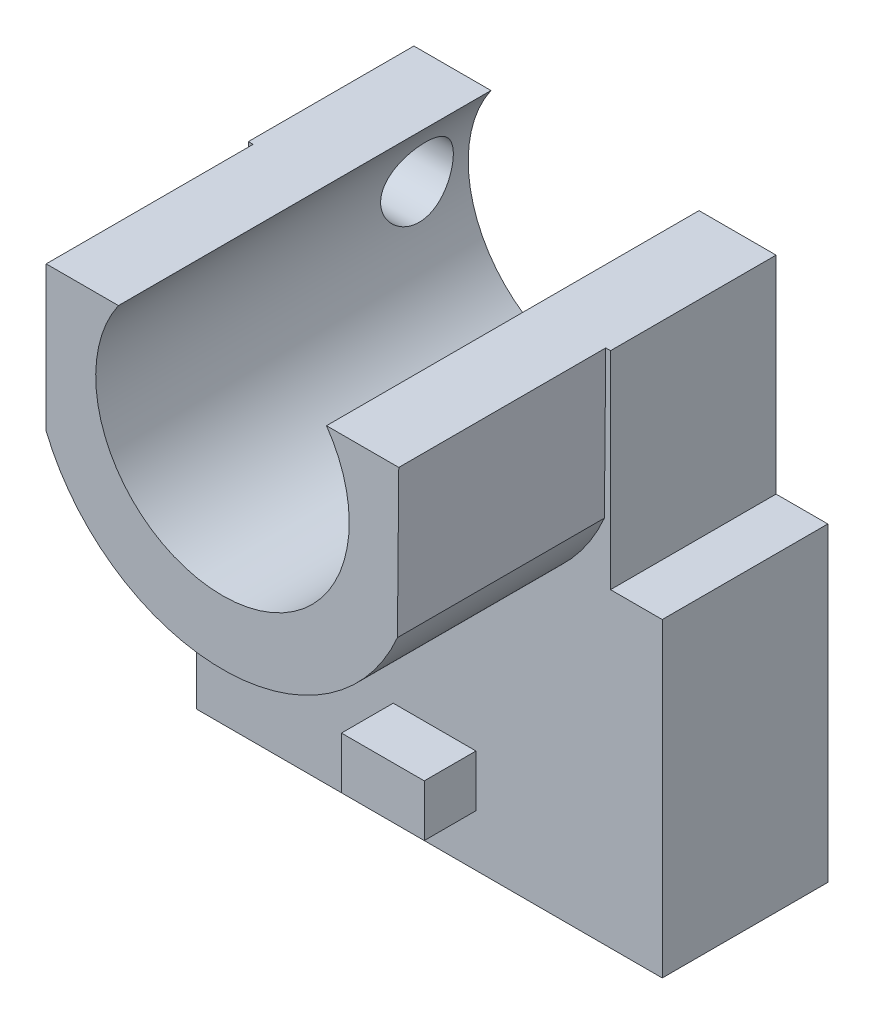
SolidWorks part; units mm, degrees
ref_plane "Front Plane" through (0, 0, 0) normal (0, 0, 1) x (1, 0, 0)
ref_plane "Top Plane" through (0, 0, 0) normal (0, 1, 0) x (1, 0, 0)
ref_plane "Right Plane" through (0, 0, 0) normal (1, 0, 0) x (0, 0, -1)
sketch "Sketch1" plane through (0, 0, 0) normal (0, 0, 1) x (1, 0, 0)
  line L0 (17.5, 15) -> (22.5, 15)
  line L1 (-22.5, -15) -> (22.5, -15)
  line L2 (-22.5, -15) -> (-22.5, 15)
  line L3 (-22.5, 15) -> (-17.5, 15)
  line L4 (22.5, -15) -> (22.5, 15)
  line L5 (-22.5, -15) -> (22.5, 15) construction
  line L6 (-22.5, 15) -> (22.5, -15) construction
  line L8 (-17.5, 15) -> (-17.5, 35)
  line L9 (-17.5, 35) -> (17.5, 35)
  line L10 (17.5, 15) -> (17.5, 35)
  point P0 (0, 0)
  dimension "D1" = 5
  dimension "D2" = 5
  dimension "D3" = 45
  dimension "D4" = 20
  dimension "D5" = 30
extrude "Boss-Extrude1" add sketch "Sketch1" along normal blind 16
sketch "Sketch2" plane through (0, 0, 16) normal (0, 0, 1) x (1, 0, 0)
  line L1 (4.5, -5) -> (-3.5, -5)
  line L2 (4.5, -5) -> (4.5, -10)
  line L3 (4.5, -10) -> (-3.5, -10)
  line L4 (-3.5, -5) -> (-3.5, -10)
  line L5 (4.5, -5) -> (-3.5, -10) construction
  line L6 (4.5, -10) -> (-3.5, -5) construction
  line L7 (-22.5, 15) -> (-22.5, -15) construction
  line L8 (-17.5, 15) -> (-22.5, 15) construction
  point P0 (0.5, -7.5)
  point P5 (0, 0)
  point P7 (0, 0)
  point P9 (-22.5, 0)
  point P12 (-20, 15)
  dimension "D1" = 8
  dimension "D2" = 5
  dimension "D3" = 19
  dimension "D4" = 20
extrude "Boss-Extrude2" add sketch "Sketch2" along normal blind 5 contours L3 L4 L1 L2
sketch "Sketch3" plane through (0, 0, 16) normal (0, 0, 1) x (1, 0, 0)
  line L0 (17.5, 35) -> (-17.5, 35) construction
  line L1 (-17.5, 35) -> (-17.5, 15) construction
  circle A0 centre (0, 28) radius 12.25
  point P4 (0, 35)
  dimension "D1" = 7
  dimension "D2" = 24.5
  dimension "D3" = 17.5
extrude "Cut-Extrude1" cut sketch "Sketch3" against normal blind 16 contours A0
sketch "Sketch4" plane through (0, 0, 16) normal (0, 0, 1) x (1, 0, 0)
  line L0 (-17.0367, 35) -> (-17.0367, 21)
  line L1 (17.0367, 35) -> (10.053, 35) construction
  line L2 (17.5, 35) -> (10.053, 35) construction
  line L3 (-10.053, 35) -> (-17.5, 35) construction
  line L4 (-17.0367, 35) -> (-10.053, 35)
  line L5 (-10.053, 35) -> (-17.0367, 35) construction
  line L6 (10.053, 35) -> (17.0367, 35)
  line L7 (17.0367, 35) -> (16.9066, 20.6913)
  arc A0 (-10.053, 35) -> (10.053, 35) centre (0, 28) ccw
  arc A1 (-17.0367, 21) -> (16.9066, 20.6913) centre (0, 28) ccw
sketch "Sketch5" plane through (0, 35, 0) normal (0, 1, 0) x (1, 0, 0)
extrude "Boss-Extrude3" add sketch "Sketch4" along normal blind 20
sketch "Sketch6" plane through (-17.5, 0, 0) normal (-1, 0, 0) x (0, 0, 1)
  line L0 (16, 35) -> (0, 35) construction
  line L1 (0, 35) -> (0, 15) construction
  circle A0 centre (5, 29) radius 3.5
  point P2 (0, 0)
  dimension "D1" = 7
  dimension "D2" = 6
  dimension "D3" = 5
extrude "Cut-Extrude2" cut sketch "Sketch6" against normal blind 8 and the other way blind 1
